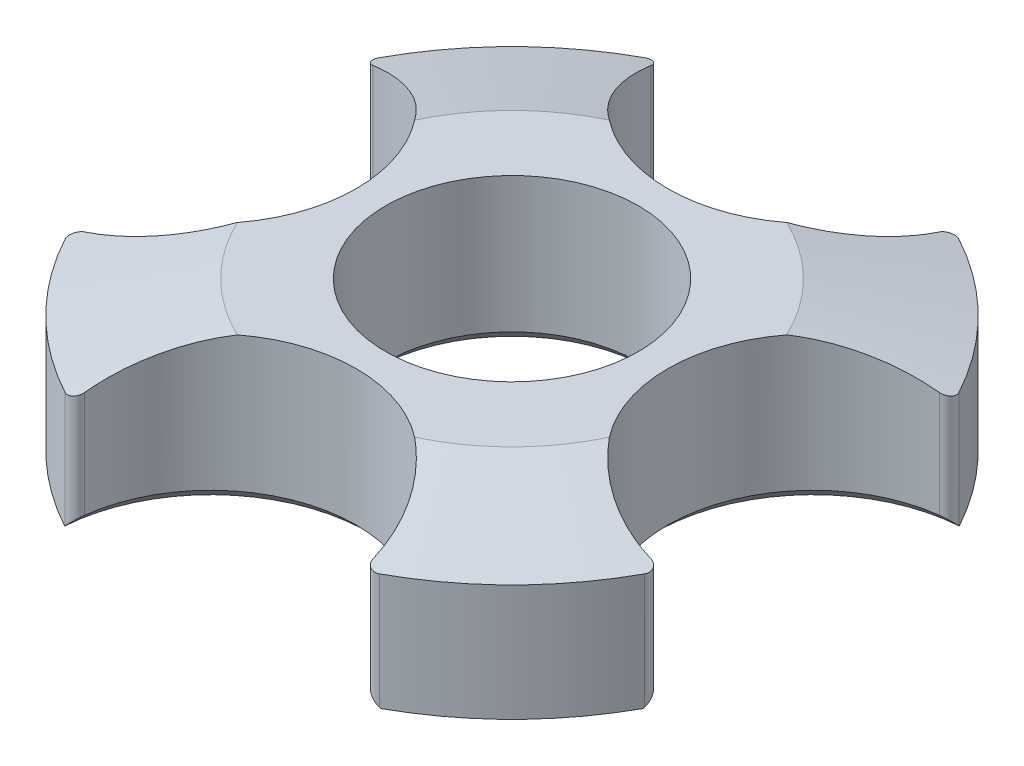
SolidWorks part; units mm, degrees
other "Markup1"
sketch "Sketch9" plane through (-16.8095, -0.0015, 16.8095) normal (0, 0, 1) x (1, 0, 0)
material "Markforged"
ref_plane "Front Plane" through (0, 0, 0) normal (0, 0, 1) x (1, 0, 0)
ref_plane "Top Plane" through (0, 0, 0) normal (0, 1, 0) x (1, 0, 0)
ref_plane "Right Plane" through (0, 0, 0) normal (1, 0, 0) x (0, 0, -1)
sketch "Sketch5" plane through (0, 0, 0) normal (0, 0, 1) x (1, 0, 0)
  line L0 (0, 0) -> (-25.4, 0)
  line L1 (0, 8.5852) -> (-11.9062, 8.5852)
  line L2 (0, 8.5852) -> (0, 0)
  line L4 (-25.4, 5.08) -> (-25.4, 0)
  line L5 (-25.4, 0) -> (-25.4, 5.08) construction
  spline S0 degree 1 poles (-25.4, 5.08) (-11.9062, 8.5852) knots 0 0 1 1
  dimension "D1" = 8.5852
  dimension "D2" = 25.4
  dimension "D3" = 11.9062
  dimension "D4" = 5.08
revolve "Revolve1" add sketch "Sketch5" angle 360 about L2
sketch "Sketch6" plane through (0, 0, 0) normal (0, -1, 0) x (1, 0, 0)
  line L1 (4.1978, 10.1283) -> (8.3955, 17.399) construction
  line L2 (8.3955, 17.399) -> (4.1978, 24.6698) construction
  line L3 (4.1978, 24.6698) -> (-4.1978, 24.6698) construction
  line L4 (-4.1978, 24.6698) -> (-8.3955, 17.399) construction
  line L5 (-8.3955, 17.399) -> (-4.1978, 10.1283) construction
  line L6 (-4.1978, 10.1283) -> (4.1978, 10.1283) construction
  circle A0 centre (0, 17.399) radius 8.3955
  circle A1 centre (0, 17.399) radius 7.2707 construction
  dimension "D1" = 17.399
  dimension "D2" = 14.5415
extrude "Cut-Extrude2" cut sketch "Sketch6" against normal through all
ref_axis "Axis1" through (0, 0, 0) along (0, 1, 0)
pattern_circular "CirPattern1" count 4 over 360 about axis through (0, 0, 0) along (0, 1, 0) of "Cut-Extrude2"
sketch "Sketch7" plane through (0, 0, 0) normal (0, -1, 0) x (1, 0, 0)
  circle A0 centre (0, 0) radius 7.3025
  dimension "D1" = 14.605
extrude "Cut-Extrude3" cut sketch "Sketch7" against normal through all
chamfer "Chamfer1" distance 0.762 angle 45 9 edges at (17.9605, 0, -17.9605) (0, 0, -9.0035) (-17.9605, 0, -17.9605) (-9.0035, 0, 0) (-17.9605, 0, 17.9605) (0, 0, 9.0035) (17.9605, 0, 17.9605) (9.0035, 0, 0) (0, 0, -7.3025)
sketch "Sketch8" plane through (0, 8.5852, 0) normal (0, 1, 0) x (1, 0, 0)
  circle A0 centre (0, 0) radius 19.05
  circle A1 centre (0, 0) radius 38.1
  dimension "D1" = 38.1
  dimension "D2" = 76.2
extrude "Cut-Extrude4" cut sketch "Sketch8" against normal through all
fillet "Fillet1" radius 0.508 8 edges at (17.1028, 3.7458, -8.3903) (17.1028, 3.7458, 8.3903) (-8.3903, 3.7458, -17.1028) (8.3903, 3.7458, -17.1028) (-17.1028, 3.7458, 8.3903) (-17.1028, 3.7458, -8.3903) (-8.3903, 3.7458, 17.1028) (8.3903, 3.7458, 17.1028)
equation "\"D2@Sketch6\"=(9/16)+.01"
